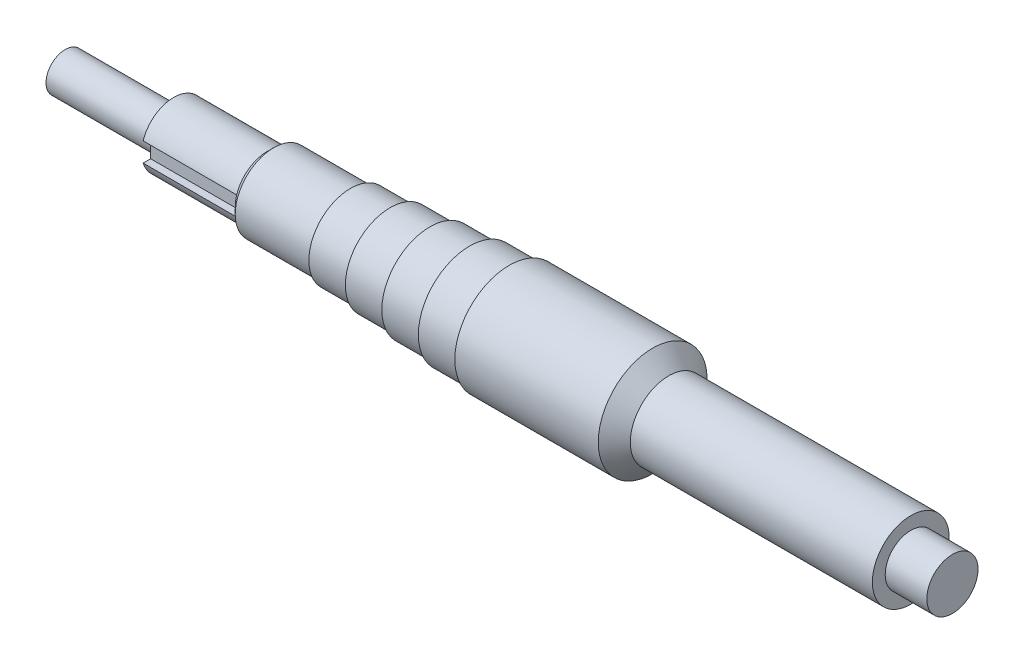
SolidWorks part; units mm, degrees
ref_plane "Front Plane" through (0, 0, 0) normal (0, 0, 1) x (1, 0, 0)
ref_plane "Top Plane" through (0, 0, 0) normal (0, 1, 0) x (1, 0, 0)
ref_plane "Right Plane" through (0, 0, 0) normal (1, 0, 0) x (0, 0, -1)
sketch "Sketch1" plane through (0, 0, 0) normal (0, 0, 1) x (1, 0, 0)
  line L0 (0, 0) -> (138.56, 0) construction
  line L4 (0, 0) -> (0, 3)
  line L5 (0, 3) -> (6.5, 3)
  line L11 (32.55, 6) -> (44.55, 6)
  line L12 (44.55, 6) -> (44.55, 6.5)
  line L13 (44.55, 6.5) -> (50.75, 6.5)
  line L17 (56.95, 7.5) -> (63.15, 7.5)
  line L18 (63.15, 7.5) -> (63.15, 8)
  line L31 (32.55, 6) -> (44.55, 6)
  line L36 (0, 0) -> (138.56, 0)
  line L38 (21.87, 5) -> (31.55, 5)
  line L40 (31.55, 5) -> (32.55, 6)
  line L41 (63.15, 8) -> (69.35, 8)
  line L42 (69.35, 8.5) -> (69.35, 8)
  line L43 (69.35, 8.5) -> (91.75, 8.5)
  line L44 (50.75, 6.5) -> (50.75, 7)
  line L45 (50.75, 7) -> (56.95, 7)
  line L46 (120.06, 6) -> (132.06, 6)
  line L47 (56.95, 7) -> (56.95, 7.5)
  line L48 (91.75, 8.5) -> (94.25, 6)
  line L49 (94.25, 6) -> (120.06, 6)
  line L50 (132.06, 6) -> (132.06, 4)
  line L51 (132.06, 4) -> (138.56, 4)
  line L52 (138.56, 4) -> (138.56, 0)
  line L54 (6.5, 3) -> (16.94, 3)
  line L55 (16.94, 3) -> (16.94, 5)
  line L56 (16.94, 5) -> (21.87, 5)
  dimension "D13" = 3
  dimension "D12" = 6.5
  dimension "D5" = 9.68
  dimension "D6" = 5
  dimension "D7" = 6
  dimension "D8" = 45
  dimension "D9" = 12
  dimension "D10" = 6.2
  dimension "D3" = 6.2
  dimension "D4" = 6.2
  dimension "D15" = 22.4
  dimension "D18" = 8.5
  dimension "D11" = 25.81
  dimension "D19" = 6
  dimension "D20" = 45
  dimension "D21" = 6.2
  dimension "D16" = 12
  dimension "D17" = 4
  dimension "D22" = 6.5
  dimension "D14" = 10.44
  dimension "D23" = 4.93
revolve "Revolve1" add sketch "Sketch1" angle 360 about L0
sketch3d "3DSketch1" plane through (0, 0, 0) normal (0, 0, 1) x (1, 0, 0)
sketch "Sketch2" plane through (0, 0, 3) normal (0, 0, 1) x (1, 0, 0)
  line L0 (31.55, 5) -> (31.55, -5) construction
  line L1 (16.94, 1.5) -> (31.55, 1.5)
  line L2 (16.94, 1.5) -> (16.94, -1.5)
  line L3 (16.94, -1.5) -> (31.55, -1.5)
  line L4 (31.55, 1.5) -> (31.55, -1.5)
  line L5 (31.55, 5) -> (16.94, 5) construction
  line L6 (16.94, 3) -> (16.94, -3) construction
  dimension "D2" = 3
  dimension "D3" = 3.5
extrude "Cut-Extrude1" cut sketch "Sketch2" against normal blind 1.4 from offset 2
equation "\"Lab_Seal_Height\"= 0.089mm"
equation "\"Lab_Seal_Width\"= 12.7mm"
equation "\"LOx_Nut_Rad\"= 3mm"
equation "\"LOx_Nut_Len\"= 6.5mm"
equation "\"LOx_Taper_Len\"= 15.24mm"
equation "\"D13@Sketch1\"=\"LOx_Nut_Rad\""
equation "\"D12@Sketch1\"=\"LOx_Nut_Len\""
equation "\"LOx_Section_2\"= 9.68"
equation "\"LOx_End_Taper_Ang\"= 45deg"
equation "\"LOx_End_Rad\"= 5mm"
equation "\"D6@Sketch1\"=\"LOx_End_Rad\""
equation "\"D5@Sketch1\"=\"LOx_Section_2\""
equation "\"LOx_Bearing_Rad\"= 6mm"
equation "\"LOx_Bearing_Section_Width\"= 12mm"
equation "\"Lab_Seal_Len\"= 6.2mm"
equation "\"Lab_Seal_Stepup\"= .5"
equation "\"D7@Sketch1\"=\"LOx_Bearing_Rad\""
equation "\"D8@Sketch1\"=\"LOx_End_Taper_Ang\""
equation "\"D9@Sketch1\"=\"LOx_Bearing_Section_Width\""
equation "\"D10@Sketch1\"=\"Lab_Seal_Len\""
equation "\"D3@Sketch1\"=\"Lab_Seal_Len\""
equation "\"D4@Sketch1\"=\"Lab_Seal_Len\""
equation "\"Center_Section_Len\"= 22.4mm"
equation "\"Center_Section_Rad\"= 8.5mm"
equation "\"D15@Sketch1\"=\"Center_Section_Len\""
equation "\"D18@Sketch1\"=\"Center_Section_Rad\""
equation "\"Kero_Len\"= 25.81"
equation "\"Kero_Rad\"= 6mm"
equation "\"D11@Sketch1\"=\"Kero_Len\""
equation "\"D19@Sketch1\"=\"Kero_Rad\""
equation "\"D20@Sketch1\"=\"LOx_End_Taper_Ang\""
equation "\"D21@Sketch1\"=\"Lab_Seal_Len\""
equation "\"Shaft_Sleeve_Nut_Size\"= 4mm"
equation "\"Shaft_Sleeve_Nut_Width\"= 6.5mm"
equation "\"Distance to connection\"= 12mm"
equation "\"D16@Sketch1\"=\"Distance to connection\""
equation "\"D17@Sketch1\"=\"Shaft_Sleeve_Nut_Size\""
equation "\"D22@Sketch1\"=\"Shaft_Sleeve_Nut_Width\""
equation "\"LOx_Small_Section_Len\"= 10.44mm"
equation "\"D14@Sketch1\"=\"LOx_Small_Section_Len\""
equation "\"LOx_Keyway_Overhand\"= 4.93mm"
equation "\"D23@Sketch1\"=\"LOx_Keyway_Overhand\""
